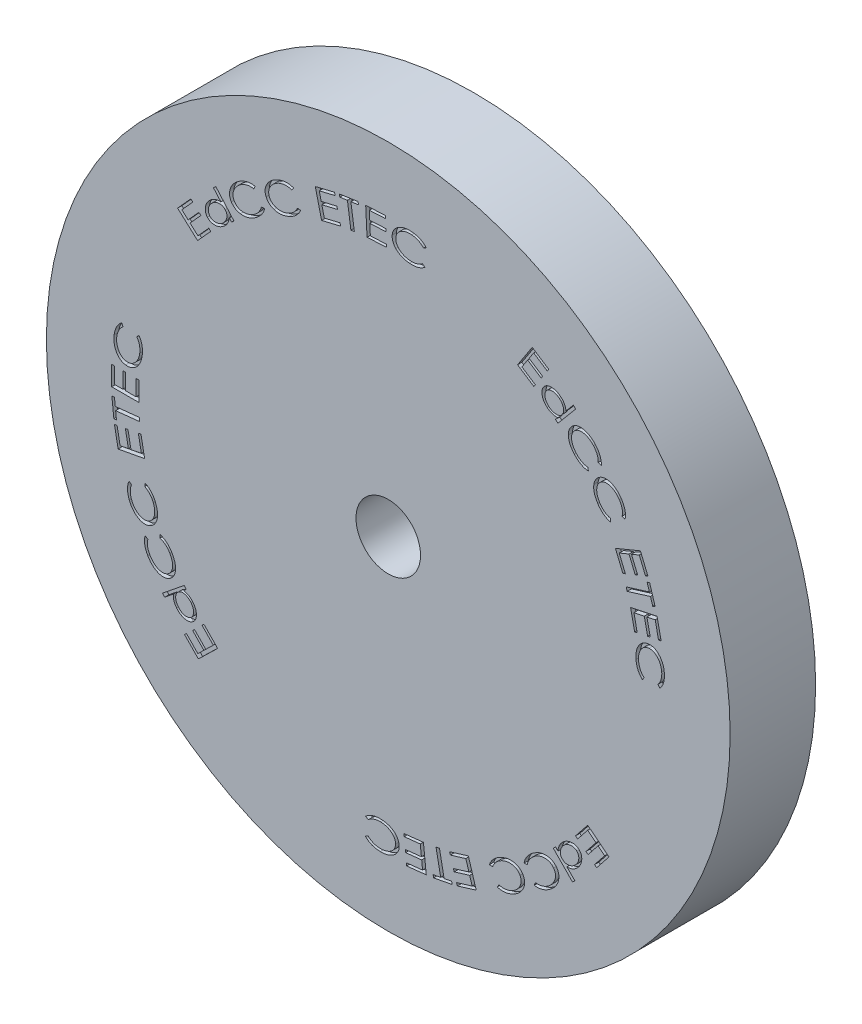
SolidWorks part; units mm, degrees
ref_plane "Front Plane" through (0, 0, 0) normal (0, 0, 1) x (1, 0, 0)
ref_plane "Top Plane" through (0, 0, 0) normal (0, 1, 0) x (1, 0, 0)
ref_plane "Right Plane" through (0, 0, 0) normal (1, 0, 0) x (0, 0, -1)
sketch "Sketch1" plane through (0, 0, 0) normal (0, 0, 1) x (1, 0, 0)
  circle A0 centre (0, 0) radius 3.775
  circle A1 centre (0, 0) radius 40
  dimension "D1" = 80
  dimension "D2" = 7.55
extrude "Boss-Extrude1" add sketch "Sketch1" along normal blind 10
sketch "Sketch2" plane through (0, 0, 0) normal (0, 0, -1) x (-1, 0, 0)
  circle A0 centre (0, 0) radius 8.775
  circle A1 centre (0, 0) radius 38
  circle A2 centre (0, 0) radius 40 construction
  circle A3 centre (0, 0) radius 3.775 construction
  dimension "D1" = 2
  dimension "D2" = 5
extrude "Cut-Extrude1" cut sketch "Sketch2" against normal blind 8
fillet "Fillet1" radius 10 2 edges at (-8.775, 0, 8) (-38, 0, 8)
sketch "Sketch3" plane through (0, 0, 10) normal (0, 0, 1) x (1, 0, 0)
  text T0 "EdCC ETEC            EdCC ETEC         EdCC ETEC       EdCC ETEC" font "Century Gothic" height 3.175
extrude "Cut-Extrude3" cut sketch "Sketch3" against normal blind 0.5
